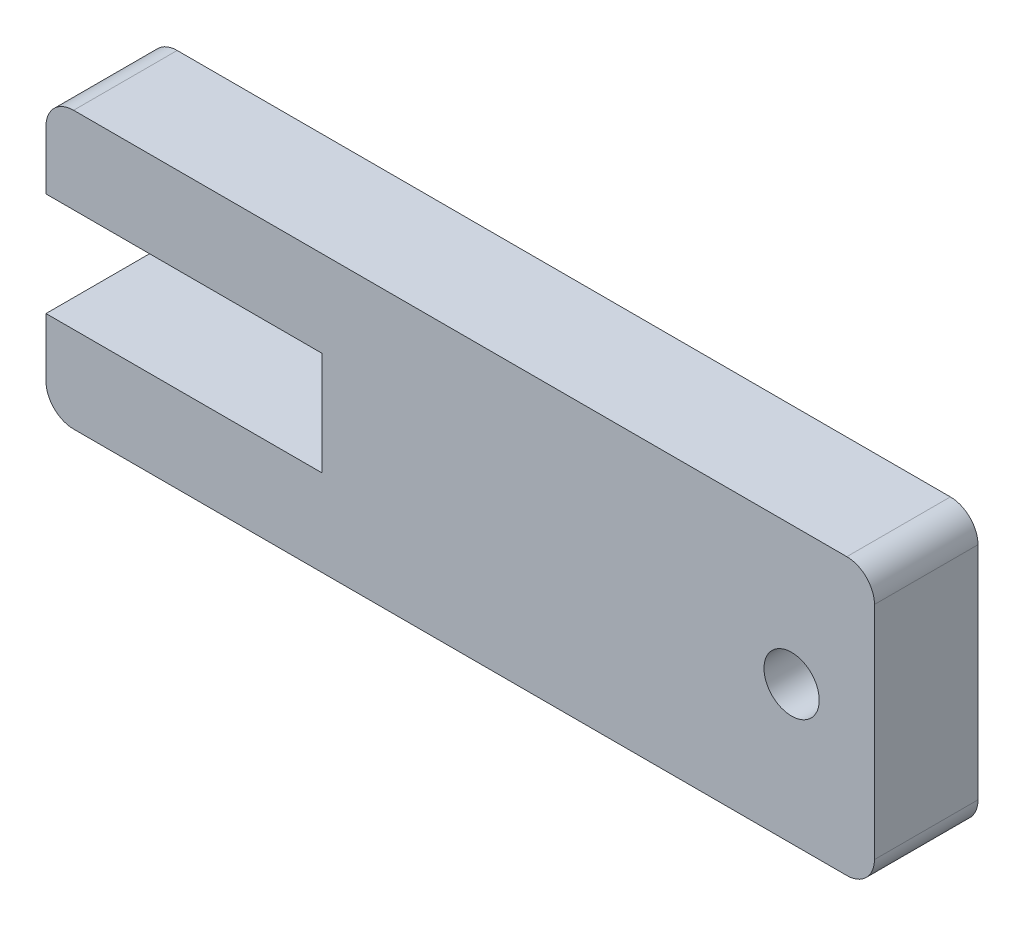
SolidWorks part; units mm, degrees
material "Corrugated Paper"
ref_plane "Front Plane" through (0, 0, 0) normal (0, 0, 1) x (1, 0, 0)
ref_plane "Top Plane" through (0, 0, 0) normal (0, 1, 0) x (1, 0, 0)
ref_plane "Right Plane" through (0, 0, 0) normal (1, 0, 0) x (0, 0, -1)
sketch "Sketch1" plane through (0, 0, 0) normal (0, 0, 1) x (1, 0, 0)
  line L0 (-12.7, 2.3813) -> (-12.7, 6.35)
  line L1 (-12.7, -2.3813) -> (0, -2.3813)
  line L3 (-12.7, 2.3813) -> (0, 2.3813)
  line L4 (0, -2.3813) -> (0, 2.3813)
  line L5 (-12.7, 6.35) -> (25.4, 6.35)
  line L6 (0, 0) -> (25.4, 0) construction
  line L7 (25.4, 6.35) -> (25.4, -6.35)
  line L8 (-12.7, -6.35) -> (25.4, -6.35)
  line L9 (-12.7, -2.3813) -> (-12.7, -6.35)
  dimension "D2" = 4.7625
  dimension "D3" = 25.4
  dimension "D4" = 12.7
extrude "Boss-Extrude1" add sketch "Sketch1" along normal mid plane 4.7625
fillet "Fillet1" radius 1.27 4 edges at (-12.7, -6.35, 0) (25.4, -6.35, 0) (25.4, 6.35, 0) (-12.7, 6.35, 0)
sketch "Sketch2" plane through (0, 0, 2.3813) normal (0, 0, 1) x (1, 0, 0)
  line L0 (0, 0) -> (25.4, 0) construction
  line L1 (25.4, -5.08) -> (25.4, 5.08) construction
  circle A0 centre (21.59, 0) radius 1.27
  dimension "D1" = 2.54
  dimension "D2" = 2.54
extrude "Cut-Extrude1" cut sketch "Sketch2" against normal through all
equation "\"D2@Sketch1\" = \"thick\""
equation "\"D1@Sketch2\" = \"rodThick\""
equation "\"D1@Boss-Extrude1\"= \"thick\""
equation "\"rodThick\"= 0.1in"
equation "\"thick\"= 3 / 16"
